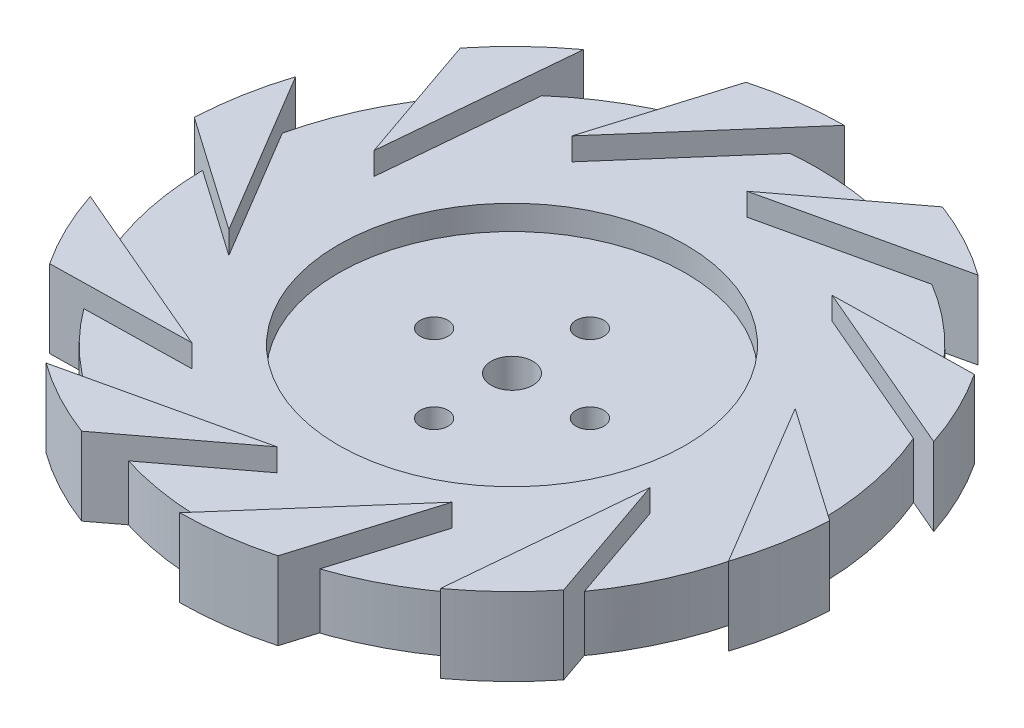
SolidWorks part; units mm, degrees
ref_plane "Front Plane" through (0, 0, 0) normal (0, 0, 1) x (1, 0, 0)
ref_plane "Top Plane" through (0, 0, 0) normal (0, 1, 0) x (1, 0, 0)
ref_plane "Right Plane" through (0, 0, 0) normal (1, 0, 0) x (0, 0, -1)
sketch "Sketch3" plane through (0, 0, 0) normal (0, 0, 1) x (1, 0, 0)
  line L0 (0, 0) -> (0, 40.1505) construction
  line L1 (-69.85, 16.0734) -> (-39.624, 16.0734)
  line L2 (-39.624, 16.0734) -> (-39.624, 10.4854)
  line L3 (-39.624, 10.4854) -> (0, 10.4854)
  line L4 (0, 10.4854) -> (0, 3.3734)
  line L5 (0, 3.3734) -> (-69.85, 3.3734)
  line L6 (-69.85, 3.3734) -> (-69.85, 16.0734)
  dimension "D1" = 12.7
  dimension "D2" = 69.85
  dimension "D3" = 39.624
  dimension "D4" = 5.588
revolve "Body" add sketch "Sketch3" angle 360 about L0
sketch "Sketch4" plane through (0, 0, 0) normal (0, 1, 0) x (1, 0, 0)
  line L0 (1.5533, 52.0769) -> (26.9502, 71.275)
  line L2 (44.4909, 61.8627) -> (1.5533, 52.0769)
  circle A1 centre (0, 0) radius 76.2 construction
  arc A3 (26.9502, 71.275) -> (44.4909, 61.8627) centre (0, 0) cw
extrude "Guide Vanes" add sketch "Sketch4" along direction (0, 1, 0) on the side of the normal blind 15.24 and the other way blind 2.54 from offset 5.969
pattern_circular "CirPattern4" count 10 over 360 about axis through (0, 16.0734, 0) along (0, -1, 0) of "Guide Vanes"
sketch "Sketch5" plane through (0, 3.3734, 0) normal (0, -1, 0) x (1, 0, 0)
  circle A0 centre (0, 0) radius 60.325
  dimension "D1" = 120.65
sketch "Sketch6" plane through (0, 0, 0) normal (0, 1, 0) x (1, 0, 0)
  circle A0 centre (0, 17.78) radius 3.175
  dimension "D1" = 6.35
  dimension "D2" = 17.78
extrude "Cut-Extrude1" cut sketch "Sketch6" along normal blind 13.97
pattern_circular "CirPattern5" count 4 over 360 about axis through (0, 16.0734, 0) along (0, -1, 0) of "Cut-Extrude1"
sketch "Sketch9" plane through (0, 10.4854, 0) normal (0, 1, 0) x (1, 0, 0)
  circle A0 centre (0, 0) radius 4.7625
  dimension "D1" = 9.525
extrude "Cut-Extrude2" cut sketch "Sketch9" against normal blind 7.62
sketch "Sketch8" plane through (0, 0, 0) normal (0, 1, 0) x (1, 0, 0)
  circle A0 centre (0, 0) radius 76.2 construction
